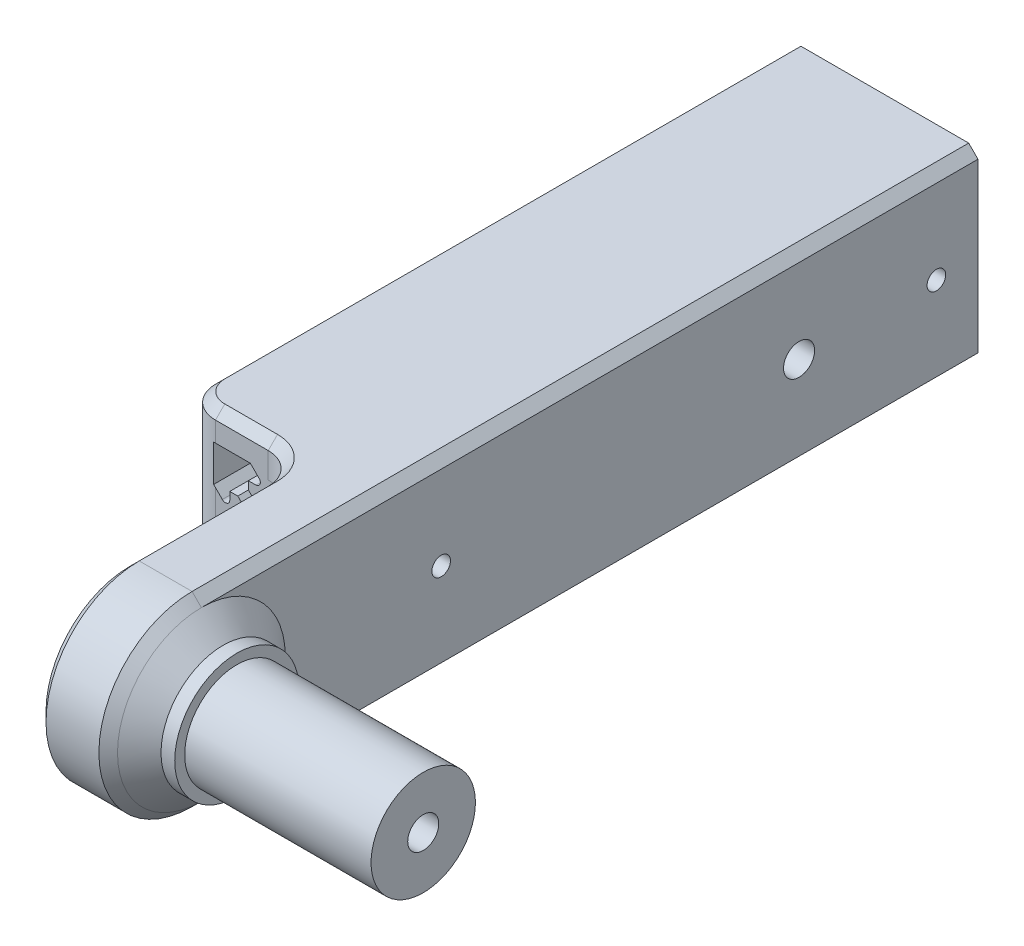
SolidWorks part; units mm, degrees
ref_plane "Front Plane" through (0, 0, 0) normal (0, 0, 1) x (1, 0, 0)
ref_plane "Top Plane" through (0, 0, 0) normal (0, 1, 0) x (1, 0, 0)
ref_plane "Right Plane" through (0, 0, 0) normal (1, 0, 0) x (0, 0, -1)
sketch "Sketch1" plane through (0, 0, 0) normal (0, 0, 1) x (1, 0, 0)
  line L0 (17.8029, 19.5) -> (12.1971, 19.5)
  line L1 (0, 0) -> (30, 0)
  line L2 (0, 0) -> (0, 30)
  line L3 (0, 30) -> (30, 30)
  line L4 (30, 0) -> (30, 30)
  line L5 (12.1971, 19.5) -> (10.2899, 21.4071)
  line L6 (10.2899, 21.4071) -> (10.2899, 22.7)
  line L7 (10.2899, 22.7) -> (11.5172, 22.7)
  line L8 (12.0121, 23.895) -> (10.6121, 25.295)
  line L9 (4.705, 19.3879) -> (6.105, 17.9879)
  line L10 (7.3, 18.4828) -> (7.3, 19.7101)
  line L11 (7.3, 19.7101) -> (8.5929, 19.7101)
  line L12 (8.5929, 19.7101) -> (10.5, 17.8029)
  line L13 (10.5, 17.8029) -> (10.5, 12.1971)
  line L14 (10.5, 12.1971) -> (8.5929, 10.2899)
  line L15 (8.5929, 10.2899) -> (7.3, 10.2899)
  line L16 (7.3, 10.2899) -> (7.3, 11.5172)
  line L17 (6.105, 12.0121) -> (4.705, 10.6121)
  line L18 (10.6121, 4.705) -> (12.0121, 6.105)
  line L19 (11.5172, 7.3) -> (10.2899, 7.3)
  line L20 (10.2899, 7.3) -> (10.2899, 8.5929)
  line L21 (10.2899, 8.5929) -> (12.1971, 10.5)
  line L22 (12.1971, 10.5) -> (17.8029, 10.5)
  line L23 (10.6121, 4.705) -> (4.705, 4.705)
  line L24 (4.705, 4.705) -> (4.705, 10.6121)
  line L25 (4.705, 19.3879) -> (4.705, 25.295)
  line L26 (4.705, 25.295) -> (10.6121, 25.295)
  line L27 (15, 28.3991) -> (15, -1.6009) construction
  line L28 (25.295, 25.295) -> (19.3879, 25.295)
  line L29 (25.295, 19.3879) -> (25.295, 25.295)
  line L30 (25.295, 4.705) -> (25.295, 10.6121)
  line L31 (19.3879, 4.705) -> (25.295, 4.705)
  line L32 (19.7101, 8.5929) -> (17.8029, 10.5)
  line L33 (19.7101, 7.3) -> (19.7101, 8.5929)
  line L34 (18.4828, 7.3) -> (19.7101, 7.3)
  line L35 (19.3879, 4.705) -> (17.9879, 6.105)
  line L36 (23.895, 12.0121) -> (25.295, 10.6121)
  line L37 (22.7, 10.2899) -> (22.7, 11.5172)
  line L38 (21.4071, 10.2899) -> (22.7, 10.2899)
  line L39 (19.5, 12.1971) -> (21.4071, 10.2899)
  line L40 (19.5, 17.8029) -> (19.5, 12.1971)
  line L41 (21.4071, 19.7101) -> (19.5, 17.8029)
  line L42 (22.7, 19.7101) -> (21.4071, 19.7101)
  line L43 (22.7, 18.4828) -> (22.7, 19.7101)
  line L44 (25.295, 19.3879) -> (23.895, 17.9879)
  line L45 (17.9879, 23.895) -> (19.3879, 25.295)
  line L46 (19.7101, 22.7) -> (18.4828, 22.7)
  line L47 (19.7101, 21.4071) -> (19.7101, 22.7)
  line L48 (17.8029, 19.5) -> (19.7101, 21.4071)
  line L49 (10.5, 15) -> (19.5, 15) construction
  arc A1 (17.9879, 6.105) -> (18.4828, 7.3) centre (18.4828, 6.6) cw
  arc A2 (11.5172, 22.7) -> (12.0121, 23.895) centre (11.5172, 23.4) ccw
  arc A3 (22.7, 11.5172) -> (23.895, 12.0121) centre (23.4, 11.5172) cw
  arc A4 (23.895, 17.9879) -> (22.7, 18.4828) centre (23.4, 18.4828) cw
  arc A5 (6.105, 17.9879) -> (7.3, 18.4828) centre (6.6, 18.4828) ccw
  arc A6 (7.3, 11.5172) -> (6.105, 12.0121) centre (6.6, 11.5172) ccw
  arc A7 (18.4828, 22.7) -> (17.9879, 23.895) centre (18.4828, 23.4) cw
  arc A8 (12.0121, 6.105) -> (11.5172, 7.3) centre (11.5172, 6.6) ccw
  point P69 (19.5, 15)
  point P70 (15, 30)
  point P73 (30, 15)
  dimension "D1" = 30
  dimension "D9" = 0.7
  dimension "D18" = 0.7
  dimension "D33" = 0.7
  dimension "D2" = 30
  dimension "D3" = 5.6059
  dimension "D4" = 2.6971
  dimension "D5" = 1.2929
  dimension "D6" = 2.595
  dimension "D7" = 135
  dimension "D8" = 1.2934
  dimension "D10" = 1.9799
  dimension "D11" = 135
  dimension "D12" = 1.2272
  dimension "D13" = 5.6059
  dimension "D14" = 2.6971
  dimension "D15" = 1.2929
  dimension "D16" = 1.2272
  dimension "D17" = 1.2934
  dimension "D19" = 1.9799
  dimension "D20" = 225
  dimension "D21" = 5.9071
  dimension "D22" = 135
  dimension "D23" = 90
  dimension "D24" = 135
  dimension "D25" = 2.595
  dimension "D26" = 135
  dimension "D27" = 135
  dimension "D28" = 1.2934
  dimension "D29" = 5.9071
  dimension "D30" = 1.9799
  dimension "D31" = 135
  dimension "D32" = 1.2934
  dimension "D34" = 1.2272
  dimension "D35" = 90
  dimension "D36" = 135
  dimension "D37" = 1.2929
  dimension "D38" = 2.595
  dimension "D39" = 2.6971
  dimension "D40" = 5.6059
  dimension "D41" = 5.9071
extrude "Boss-Extrude3" add sketch "Sketch1" along normal blind 95
sketch "Sketch3" plane through (30, 0, 0) normal (1, 0, 0) x (0, 0, -1)
  line L1 (-95, 0) -> (-95, 30) construction
  line L2 (-125, 30) -> (-95, 30)
  line L3 (-125, 0) -> (-95, 0)
  line L8 (0, 0) -> (0, 30)
  line L9 (0, 30) -> (-95, 30)
  line L10 (-95, 30) -> (-95, 0)
  line L11 (-95, 0) -> (0, 0)
  line L14 (-95, 30) -> (-95, 0)
  arc A1 (-125, 30) -> (-125, 0) centre (-125, 15) ccw
  point P5 (-95, 15)
  dimension "D1" = 30
  dimension "D2" = 30
  dimension "D3" = 0
extrude "Boss-Extrude4" add sketch "Sketch3" against normal blind 30
sketch "Sketch4" plane through (0, 30, 0) normal (0, 1, 0) x (1, 0, 0)
  line L2 (0, -140) -> (30, -140) construction
  line L3 (5, -97.7296) -> (13.4906, -97.7296)
  line L5 (0, -140) -> (18.4906, -140)
  line L6 (18.4906, -102.7296) -> (18.4906, -140)
  line L7 (0, -92.7296) -> (0, -140)
  line L9 (0, -125) -> (0, 0) construction
  arc A1 (13.4906, -97.7296) -> (18.4906, -102.7296) centre (13.4906, -102.7296) cw
  arc A2 (5, -97.7296) -> (0, -92.7296) centre (5, -92.7296) cw
  point P16 (0, -125)
  dimension "D1" = 5
  dimension "D2" = 5
extrude "Cut-Extrude1" cut sketch "Sketch4" against normal through all
sketch "Sketch5" plane through (30, 0, 0) normal (1, 0, 0) x (0, 0, -1)
  circle A0 centre (-125, 15) radius 10
  dimension "D1" = 20
extrude "Boss-Extrude5" add sketch "Sketch5" along normal blind 5.71
sketch "Sketch6" plane through (35.71, 0, 0) normal (1, 0, 0) x (0, 0, -1)
  circle A0 centre (-125, 15) radius 8.4
  dimension "D1" = 16.8
extrude "Boss-Extrude6" add sketch "Sketch6" along normal blind 30
sketch "Sketch8" plane through (0, 0, 0) normal (-1, 0, 0) x (0, 0, 1)
  line L0 (0, 30) -> (0, 0) construction
  circle A0 centre (6.7, 15) radius 1.5
  circle A1 centre (86.4, 15) radius 1.5
  circle A2 centre (28.8, 15) radius 2.5
  circle A3 centre (125, 15) radius 2.5
  point P8 (0, 15)
  dimension "D1" = 5
  dimension "D2" = 3
  dimension "D3" = 3
  dimension "D7" = 5
  dimension "D4" = 6.7
  dimension "D5" = 22.1
  dimension "D6" = 57.6
extrude "Cut-Extrude2" cut sketch "Sketch8" against normal through all
chamfer "Chamfer1" distance 1.5 angle 45 14 edges at (30, 0, 62.5) (0, 0, 46.3648) (0, 30, 46.3648) (30, 30, 62.5) (9.2453, 0, 97.7296) (1.4645, 0, 96.2651) (9.2453, 30, 97.7296) (1.4645, 30, 96.2651) (17.0262, 0, 99.1941) (18.4906, 0, 113.8648) (18.4906, 15, 140) (18.4906, 30, 113.8648) (17.0262, 30, 99.1941) (30, 15, 140)
chamfer "Chamfer2" distance 3.5 angle 45 1 edges at (30, 15, 135)
sketch "Sketch9" plane through (0, 0, 95) normal (0, 0, -1) x (-1, 0, 0)
  line L44 (-10.6121, 4.705) -> (-4.705, 4.705)
  line L45 (-4.705, 4.705) -> (-4.705, 10.6121)
  line L46 (-4.705, 10.6121) -> (-6.105, 12.0121)
  line L47 (-7.3, 11.5172) -> (-7.3, 10.2899)
  line L48 (-7.3, 10.2899) -> (-8.5929, 10.2899)
  line L49 (-8.5929, 10.2899) -> (-10.5, 12.1971)
  line L50 (-10.5, 12.1971) -> (-10.5, 17.8029)
  line L51 (-10.5, 17.8029) -> (-8.5929, 19.7101)
  line L52 (-8.5929, 19.7101) -> (-7.3, 19.7101)
  line L53 (-7.3, 19.7101) -> (-7.3, 18.4828)
  line L54 (-6.105, 17.9879) -> (-4.705, 19.3879)
  line L55 (-4.705, 19.3879) -> (-4.705, 25.295)
  line L56 (-4.705, 25.295) -> (-10.6121, 25.295)
  line L57 (-10.6121, 25.295) -> (-12.0121, 23.895)
  line L58 (-11.5172, 22.7) -> (-10.2899, 22.7)
  line L59 (-10.2899, 22.7) -> (-10.2899, 21.4071)
  line L60 (-10.2899, 21.4071) -> (-12.1971, 19.5)
  line L61 (-12.1971, 19.5) -> (-17.8029, 19.5)
  line L62 (-17.8029, 19.5) -> (-19.7101, 21.4071)
  line L63 (-19.7101, 21.4071) -> (-19.7101, 22.7)
  line L64 (-19.7101, 22.7) -> (-18.4828, 22.7)
  line L65 (-17.9879, 23.895) -> (-19.3879, 25.295)
  line L66 (-19.3879, 25.295) -> (-25.295, 25.295)
  line L67 (-25.295, 25.295) -> (-25.295, 19.3879)
  line L68 (-25.295, 19.3879) -> (-23.895, 17.9879)
  line L69 (-22.7, 18.4828) -> (-22.7, 19.7101)
  line L70 (-22.7, 19.7101) -> (-21.4071, 19.7101)
  line L71 (-21.4071, 19.7101) -> (-19.5, 17.8029)
  line L72 (-19.5, 17.8029) -> (-19.5, 12.1971)
  line L73 (-19.5, 12.1971) -> (-21.4071, 10.2899)
  line L74 (-21.4071, 10.2899) -> (-22.7, 10.2899)
  line L75 (-22.7, 10.2899) -> (-22.7, 11.5172)
  line L76 (-23.895, 12.0121) -> (-25.295, 10.6121)
  line L77 (-25.295, 10.6121) -> (-25.295, 4.705)
  line L78 (-25.295, 4.705) -> (-19.3879, 4.705)
  line L79 (-19.3879, 4.705) -> (-17.9879, 6.105)
  line L80 (-18.4828, 7.3) -> (-19.7101, 7.3)
  line L81 (-19.7101, 7.3) -> (-19.7101, 8.5929)
  line L82 (-19.7101, 8.5929) -> (-17.8029, 10.5)
  line L83 (-17.8029, 10.5) -> (-12.1971, 10.5)
  line L84 (-12.1971, 10.5) -> (-10.2899, 8.5929)
  line L85 (-10.2899, 8.5929) -> (-10.2899, 7.3)
  line L86 (-10.2899, 7.3) -> (-11.5172, 7.3)
  line L87 (-12.0121, 6.105) -> (-10.6121, 4.705)
  line L88 (-10.6121, 4.705) -> (-4.705, 4.705)
  line L89 (-4.705, 4.705) -> (-4.705, 10.6121)
  line L90 (-4.705, 10.6121) -> (-6.105, 12.0121)
  line L91 (-7.3, 11.5172) -> (-7.3, 10.2899)
  line L92 (-7.3, 10.2899) -> (-8.5929, 10.2899)
  line L93 (-8.5929, 10.2899) -> (-10.5, 12.1971)
  line L94 (-10.5, 12.1971) -> (-10.5, 17.8029)
  line L95 (-10.5, 17.8029) -> (-8.5929, 19.7101)
  line L96 (-8.5929, 19.7101) -> (-7.3, 19.7101)
  line L97 (-7.3, 19.7101) -> (-7.3, 18.4828)
  line L98 (-6.105, 17.9879) -> (-4.705, 19.3879)
  line L99 (-4.705, 19.3879) -> (-4.705, 25.295)
  line L100 (-4.705, 25.295) -> (-10.6121, 25.295)
  line L101 (-10.6121, 25.295) -> (-12.0121, 23.895)
  line L102 (-11.5172, 22.7) -> (-10.2899, 22.7)
  line L103 (-10.2899, 22.7) -> (-10.2899, 21.4071)
  line L104 (-10.2899, 21.4071) -> (-12.1971, 19.5)
  line L105 (-12.1971, 19.5) -> (-17.8029, 19.5)
  line L106 (-17.8029, 19.5) -> (-19.7101, 21.4071)
  line L107 (-19.7101, 21.4071) -> (-19.7101, 22.7)
  line L108 (-19.7101, 22.7) -> (-18.4828, 22.7)
  line L109 (-17.9879, 23.895) -> (-19.3879, 25.295)
  line L110 (-19.3879, 25.295) -> (-25.295, 25.295)
  line L111 (-25.295, 25.295) -> (-25.295, 19.3879)
  line L112 (-25.295, 19.3879) -> (-23.895, 17.9879)
  line L113 (-22.7, 18.4828) -> (-22.7, 19.7101)
  line L114 (-22.7, 19.7101) -> (-21.4071, 19.7101)
  line L115 (-21.4071, 19.7101) -> (-19.5, 17.8029)
  line L116 (-19.5, 17.8029) -> (-19.5, 12.1971)
  line L117 (-19.5, 12.1971) -> (-21.4071, 10.2899)
  line L118 (-21.4071, 10.2899) -> (-22.7, 10.2899)
  line L119 (-22.7, 10.2899) -> (-22.7, 11.5172)
  line L120 (-23.895, 12.0121) -> (-25.295, 10.6121)
  line L121 (-25.295, 10.6121) -> (-25.295, 4.705)
  line L122 (-25.295, 4.705) -> (-19.3879, 4.705)
  line L123 (-19.3879, 4.705) -> (-17.9879, 6.105)
  line L124 (-18.4828, 7.3) -> (-19.7101, 7.3)
  line L125 (-19.7101, 7.3) -> (-19.7101, 8.5929)
  line L126 (-19.7101, 8.5929) -> (-17.8029, 10.5)
  line L127 (-17.8029, 10.5) -> (-12.1971, 10.5)
  line L128 (-12.1971, 10.5) -> (-10.2899, 8.5929)
  line L129 (-10.2899, 8.5929) -> (-10.2899, 7.3)
  line L130 (-10.2899, 7.3) -> (-11.5172, 7.3)
  line L131 (-12.0121, 6.105) -> (-10.6121, 4.705)
  arc A8 (-6.105, 12.0121) -> (-7.3, 11.5172) centre (-6.6, 11.5172) ccw
  arc A9 (-7.3, 18.4828) -> (-6.105, 17.9879) centre (-6.6, 18.4828) ccw
  arc A10 (-12.0121, 23.895) -> (-11.5172, 22.7) centre (-11.5172, 23.4) ccw
  arc A11 (-18.4828, 22.7) -> (-17.9879, 23.895) centre (-18.4828, 23.4) ccw
  arc A12 (-23.895, 17.9879) -> (-22.7, 18.4828) centre (-23.4, 18.4828) ccw
  arc A13 (-22.7, 11.5172) -> (-23.895, 12.0121) centre (-23.4, 11.5172) ccw
  arc A14 (-17.9879, 6.105) -> (-18.4828, 7.3) centre (-18.4828, 6.6) ccw
  arc A15 (-11.5172, 7.3) -> (-12.0121, 6.105) centre (-11.5172, 6.6) ccw
  arc A16 (-6.105, 12.0121) -> (-7.3, 11.5172) centre (-6.6, 11.5172) ccw
  arc A17 (-7.3, 18.4828) -> (-6.105, 17.9879) centre (-6.6, 18.4828) ccw
  arc A18 (-12.0121, 23.895) -> (-11.5172, 22.7) centre (-11.5172, 23.4) ccw
  arc A19 (-18.4828, 22.7) -> (-17.9879, 23.895) centre (-18.4828, 23.4) ccw
  arc A20 (-23.895, 17.9879) -> (-22.7, 18.4828) centre (-23.4, 18.4828) ccw
  arc A21 (-22.7, 11.5172) -> (-23.895, 12.0121) centre (-23.4, 11.5172) ccw
  arc A22 (-17.9879, 6.105) -> (-18.4828, 7.3) centre (-18.4828, 6.6) ccw
  arc A23 (-11.5172, 7.3) -> (-12.0121, 6.105) centre (-11.5172, 6.6) ccw
  dimension "D1" = 0
extrude "Cut-Extrude3" cut sketch "Sketch9" against normal blind 17
sketch "Sketch10" plane through (18.4906, 0, 0) normal (-1, 0, 0) x (0, 0, 1)
  line L1 (112, 24.3977) -> (97.7296, 24.3977)
  line L2 (112, 24.3977) -> (112, 19.5)
  line L3 (112, 19.5) -> (97.7296, 19.5)
  line L4 (97.7296, 24.3977) -> (97.7296, 19.5)
  line L5 (112, 5.6023) -> (97.7296, 5.6023)
  line L6 (112, 5.6023) -> (112, 10.5)
  line L7 (112, 10.5) -> (97.7296, 10.5)
  line L8 (97.7296, 5.6023) -> (97.7296, 10.5)
extrude "Cut-Extrude4" cut sketch "Sketch10" against normal blind 2 and the other way blind 10
